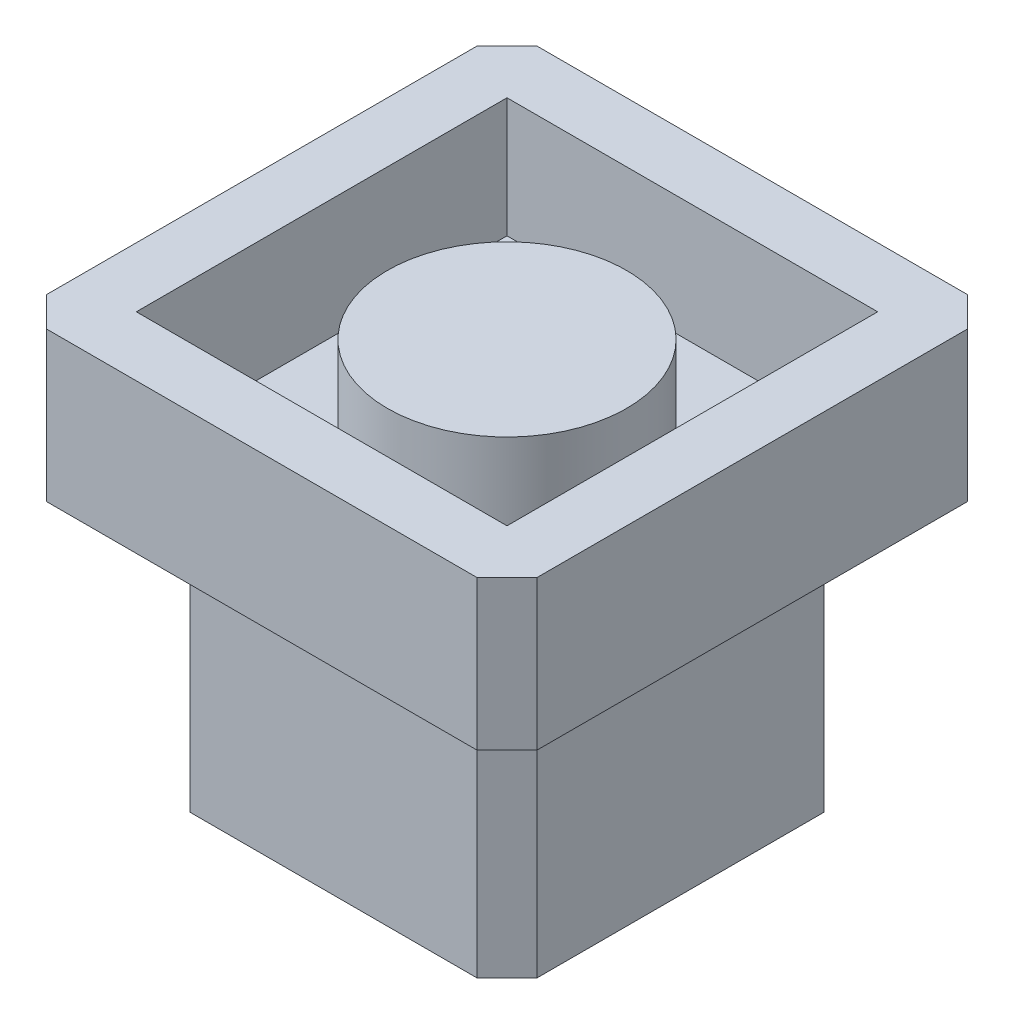
SolidWorks part; units mm, degrees
ref_plane "Front Plane" through (0, 0, 0) normal (0, 0, 1) x (1, 0, 0)
ref_plane "Top Plane" through (0, 0, 0) normal (0, 1, 0) x (1, 0, 0)
ref_plane "Right Plane" through (0, 0, 0) normal (1, 0, 0) x (0, 0, -1)
sketch "Sketch1" plane through (0, 0, 0) normal (0, 1, 0) x (1, 0, 0)
  line L0 (-4.1, 4.1) -> (-4.1, -4.1)
  line L1 (-3.1, 3.1) -> (3.1, 3.1)
  line L2 (-3.1, 3.1) -> (-3.1, -3.1)
  line L3 (-3.1, -3.1) -> (3.1, -3.1)
  line L4 (3.1, 3.1) -> (3.1, -3.1)
  line L5 (-3.1, 3.1) -> (3.1, -3.1) construction
  line L6 (-3.1, -3.1) -> (3.1, 3.1) construction
  line L7 (-4.1, -4.1) -> (4.1, -4.1)
  line L8 (4.1, 4.1) -> (4.1, -4.1)
  line L9 (-4.1, 4.1) -> (4.1, 4.1)
  circle A1 centre (0, 0) radius 2
  dimension "D1" = 4
  dimension "D2" = 6.2
  dimension "D3" = 1
extrude "Boss-Extrude1" add sketch "Sketch1" along normal blind 1.6 contours A1 region at (0, 0, 0)
extrude "Boss-Extrude2" add sketch "Sketch1<3>" along normal blind 2 separate body contours L9 L0 L7 L8 L1 L4 L3 L2 region at (0, 0, -3.984)
sketch "Sketch1<3>" plane through (0, 0, 0) normal (0, 1, 0) x (1, 0, 0) same geometry as "Sketch1"
extrude "Boss-Extrude3" add sketch "Sketch1<4>" against normal blind 0.5 contours L9 L0 L7 L8 L1 L4 L3 L2 | L4 L1 L2 L3 A1 | A1 region at (0, 0, -3.984) region at (0, 0, -3.0123) region at (0, 0, 0)
sketch "Sketch1<4>" plane through (0, 0, 0) normal (0, 1, 0) x (1, 0, 0) same geometry as "Sketch1"
sketch "Sketch3" plane through (0, -0.5, 0) normal (0, -1, 0) x (1, 0, 0)
  line L1 (-2.9, 2.9) -> (2.9, 2.9)
  line L2 (-2.9, 2.9) -> (-2.9, -2.9)
  line L3 (-2.9, -2.9) -> (2.9, -2.9)
  line L4 (2.9, 2.9) -> (2.9, -2.9)
  line L5 (-2.9, 2.9) -> (2.9, -2.9) construction
  line L6 (-2.9, -2.9) -> (2.9, 2.9) construction
  point P0 (0, 0)
  dimension "D1" = 5.8
  dimension "D2" = 5.8
extrude "Boss-Extrude4" add sketch "Sketch3" along normal blind 4.5
chamfer "Chamfer1" distance 0.5 angle 45 8 edges at (-4.1, 0.75, -4.1) (4.1, 0.75, -4.1) (-4.1, 0.75, 4.1) (4.1, 0.75, 4.1) (-2.9, -2.75, 2.9) (2.9, -2.75, 2.9) (-2.9, -2.75, -2.9) (2.9, -2.75, -2.9)
sketch "Sketch4" plane through (0, -5, 0) normal (0, -1, 0) x (1, 0, 0)
  text T1 "D"
extrude "Cut-Extrude1" cut sketch "Sketch4" against normal blind 0.2
